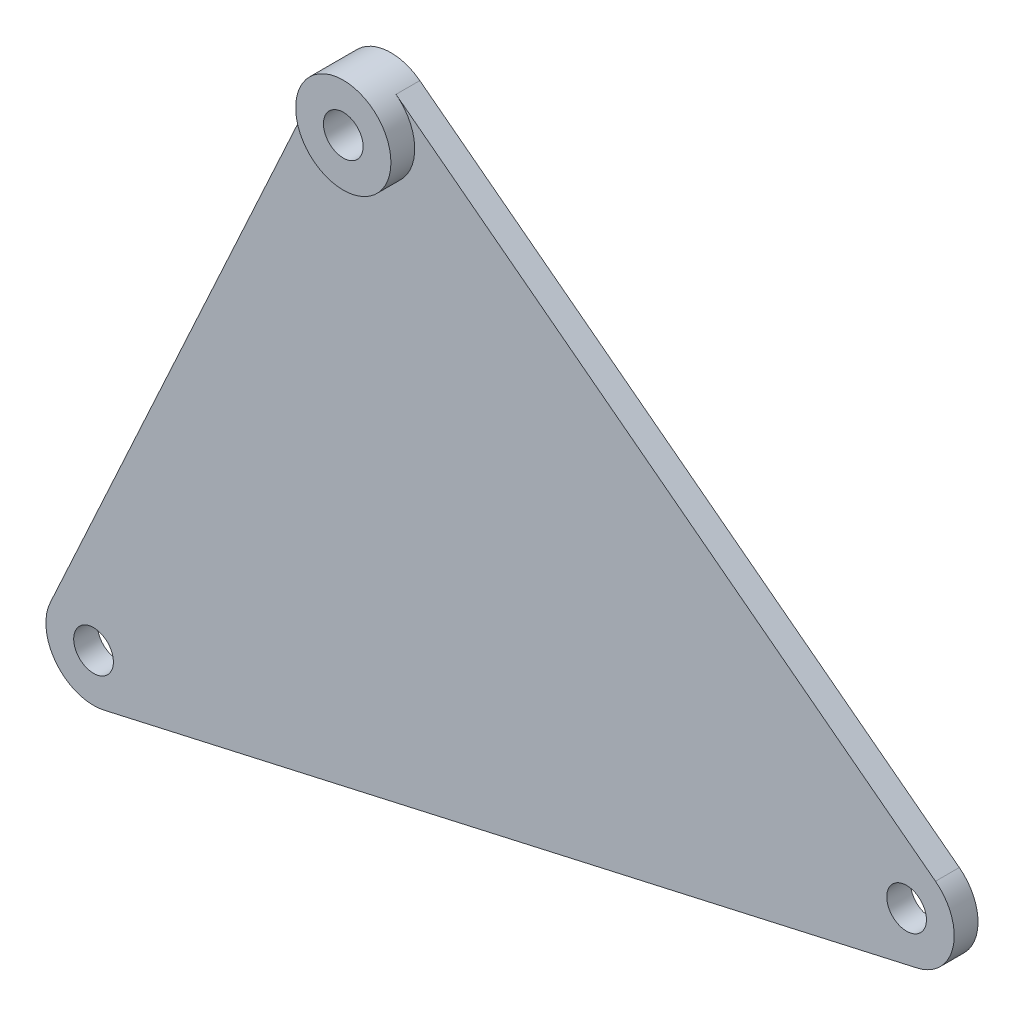
SolidWorks part; units mm, degrees
ref_plane "前视基准面" through (0, 0, 0) normal (0, 0, 1) x (1, 0, 0)
ref_plane "上视基准面" through (0, 0, 0) normal (0, 1, 0) x (1, 0, 0)
ref_plane "右视基准面" through (0, 0, 0) normal (1, 0, 0) x (0, 0, -1)
sketch "草图1" plane through (0, 0, 0) normal (0, 0, 1) x (1, 0, 0)
  line L0 (0, 0) -> (102.4311, 23.0839) construction
  line L1 (-1000, 0) -> (49000, 0) construction
  line L2 (29.0129, 77.4629) -> (-5.4514, 2.5065)
  line L3 (1.3191, -5.8532) -> (103.7502, 17.2306)
  line L4 (106.0713, 27.8535) -> (38.1045, 79.726)
  circle A0 centre (0, 0) radius 2.5
  circle A1 centre (102.4311, 23.0839) radius 2.5
  circle A2 centre (34.4643, 74.9564) radius 2.5
  circle A3 centre (0, 0) radius 6
  circle A4 centre (34.4643, 74.9564) radius 6
  circle A5 centre (102.4311, 23.0839) radius 6
  dimension "D1" = 5
  dimension "D2" = 105
  dimension "D3" = 82.5
  dimension "D4" = 85.5
  dimension "D6" = 12
  dimension "D5" = 12.7
extrude "凸台-拉伸1" add sketch "草图1" along normal blind 3 contours A5 L4 A4 L2 A3 L3 | A4 A2 | A3 A0 | A5 A1 region at (45.899, 32.0834, 0) region at (33.056, 80.614, 0) region at (1.2466, 5.6955, 0) region at (107.6568, 25.6693, 0)
extrude "凸台-拉伸2" add sketch "草图1<3>" along normal blind 3 from surface contours A4 A2 region at (33.056, 80.614, 0) starting at face at (45.5081, 33.0448, 3)
sketch "草图1<3>" plane through (0, 0, 0) normal (0, 0, 1) x (1, 0, 0) same geometry as "草图1"
